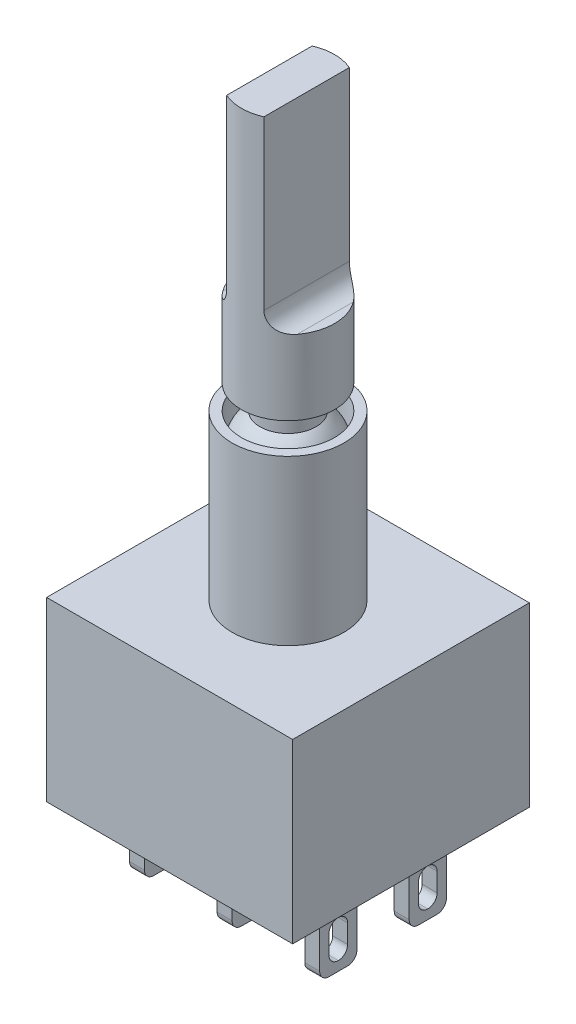
SolidWorks part; units mm, degrees
ref_plane "Спереди" through (0, 0, 0) normal (0, 0, 1) x (1, 0, 0)
ref_plane "Сверху" through (0, 0, 0) normal (0, 1, 0) x (1, 0, 0)
ref_plane "Справа" through (0, 0, 0) normal (1, 0, 0) x (0, 0, -1)
sketch "Sketch1" plane through (0, 0, 0) normal (0, 1, 0) x (1, 0, 0)
  line L1 (6.6, -6.35) -> (-6.6, -6.35)
  line L2 (6.6, -6.35) -> (6.6, 6.35)
  line L3 (6.6, 6.35) -> (-6.6, 6.35)
  line L4 (-6.6, -6.35) -> (-6.6, 6.35)
  line L5 (6.6, -6.35) -> (-6.6, 6.35) construction
  line L6 (6.6, 6.35) -> (-6.6, -6.35) construction
  point P0 (0, 0)
  dimension "D1" = 13.2
  dimension "D2" = 12.7
extrude "Boss-Extrude1" add sketch "Sketch1" along normal blind 9.5
sketch "Sketch2" plane through (0, 9.5, 0) normal (0, 1, 0) x (1, 0, 0)
  line L0 (-6.6, 6.35) -> (6.6, -6.35) construction
  circle A0 centre (0, 0) radius 3
  dimension "D1" = 6
extrude "Boss-Extrude2" add sketch "Sketch2" along normal blind 8.8
sketch "Sketch4" plane through (0, 18.3, 0) normal (0, 1, 0) x (1, 0, 0)
  circle A0 centre (0, 0) radius 2.5
  dimension "D1" = 5
extrude "Cut-Extrude1" cut sketch "Sketch4" against normal blind 2
sketch "Sketch5" plane through (0, 16.3, 0) normal (0, 1, 0) x (1, 0, 0)
  circle A0 centre (0, 0) radius 1.5
  dimension "D1" = 3
extrude "Boss-Extrude3" add sketch "Sketch5" along normal blind 5
sketch "Sketch3" plane through (0, 16.3, 0) normal (0, 1, 0) x (1, 0, 0)
  line L0 (0, -3) -> (0, 3) construction
  line L1 (0, -2.5) -> (0, 2.5)
  circle A0 centre (0, 0) radius 3 construction
  arc A1 (0, -2.5) -> (0, 2.5) centre (0, 0) cw
  point P7 (0, 0)
  dimension "D1" = 5
revolve "Revolve2" add sketch "Sketch3" angle 180 about L0
fillet "Fillet1" radius 1 1 edges at (0, 21.3, 1.5)
sketch "Sketch6" plane through (0, 0, 0) normal (0, -1, 0) x (1, 0, 0)
  line L0 (-4.7, 6.35) -> (-4.7, -6.35) construction
  line L1 (-6.6, 6.35) -> (6.6, 6.35) construction
  line L2 (6.6, -6.35) -> (-6.6, -6.35) construction
  line L3 (0, 6.35) -> (0, -6.35) construction
  line L4 (4.7, 6.35) -> (4.7, -6.35) construction
  line L6 (-6.6, 2.4) -> (6.6, 2.4) construction
  line L7 (-4.3, 1.4) -> (-5.1, 1.4)
  line L8 (-4.3, 1.4) -> (-4.3, 3.4)
  line L9 (-4.3, 3.4) -> (-5.1, 3.4)
  line L10 (-5.1, 1.4) -> (-5.1, 3.4)
  line L11 (-4.3, 1.4) -> (-5.1, 3.4) construction
  line L12 (-4.3, 3.4) -> (-5.1, 1.4) construction
  line L13 (-6.6, -6.35) -> (-6.6, 6.35) construction
  line L14 (6.6, 6.35) -> (6.6, -6.35) construction
  line L15 (-6.6, -2.4) -> (6.6, -2.4) construction
  line L16 (-6.6, 0) -> (6.6, 0) construction
  line L17 (-4.3, -3.4) -> (-5.1, -3.4)
  line L18 (-4.3, -3.4) -> (-4.3, -1.4)
  line L19 (-4.3, -1.4) -> (-5.1, -1.4)
  line L20 (-5.1, -3.4) -> (-5.1, -1.4)
  line L21 (-4.3, -3.4) -> (-5.1, -1.4) construction
  line L22 (-4.3, -1.4) -> (-5.1, -3.4) construction
  line L23 (0.4, -3.4) -> (-0.4, -3.4)
  line L24 (0.4, -3.4) -> (0.4, -1.4)
  line L25 (0.4, -1.4) -> (-0.4, -1.4)
  line L26 (-0.4, -3.4) -> (-0.4, -1.4)
  line L27 (0.4, -3.4) -> (-0.4, -1.4) construction
  line L28 (0.4, -1.4) -> (-0.4, -3.4) construction
  line L29 (0.4, 1.4) -> (-0.4, 1.4)
  line L30 (0.4, 1.4) -> (0.4, 3.4)
  line L31 (0.4, 3.4) -> (-0.4, 3.4)
  line L32 (-0.4, 1.4) -> (-0.4, 3.4)
  line L33 (0.4, 1.4) -> (-0.4, 3.4) construction
  line L34 (0.4, 3.4) -> (-0.4, 1.4) construction
  line L35 (5.1, 1.4) -> (4.3, 1.4)
  line L36 (5.1, 1.4) -> (5.1, 3.4)
  line L37 (5.1, 3.4) -> (4.3, 3.4)
  line L38 (4.3, 1.4) -> (4.3, 3.4)
  line L39 (5.1, 1.4) -> (4.3, 3.4) construction
  line L40 (5.1, 3.4) -> (4.3, 1.4) construction
  line L41 (5.1, -3.4) -> (4.3, -3.4)
  line L42 (5.1, -3.4) -> (5.1, -1.4)
  line L43 (5.1, -1.4) -> (4.3, -1.4)
  line L44 (4.3, -3.4) -> (4.3, -1.4)
  line L45 (5.1, -3.4) -> (4.3, -1.4) construction
  line L46 (5.1, -1.4) -> (4.3, -3.4) construction
  point P10 (0, 0)
  point P11 (-4.7, 2.4)
  point P27 (-4.7, -2.4)
  point P32 (0, -2.4)
  point P37 (0, 2.4)
  point P42 (4.7, 2.4)
  point P47 (4.7, -2.4)
  dimension "D1" = 4.7
  dimension "D2" = 4.7
  dimension "D3" = 2
  dimension "D4" = 0.8
  dimension "D5" = 4.8
  dimension "D6" = 2.4
extrude "Boss-Extrude4" add sketch "Sketch6" along normal blind 4
sketch "Sketch7" plane through (-5.1, 0, 0) normal (-1, 0, 0) x (0, 0, 1)
  line L0 (-2.4, -4) -> (-2.4, 0) construction
  line L1 (-1.4, -4) -> (-3.4, -4) construction
  line L2 (-1.4, 0) -> (-3.4, 0) construction
  line L3 (2.4, -4) -> (2.4, 0) construction
  line L6 (3.4, -4) -> (1.4, -4) construction
  line L7 (3.4, 0) -> (1.4, 0) construction
  line L8 (-3.4, -2.5) -> (3.4, -2.5) construction
  line L9 (-1.9, -3.5) -> (-2.9, -3.5)
  line L10 (-1.9, -3.5) -> (-1.9, -1.5)
  line L11 (-1.9, -1.5) -> (-2.9, -1.5)
  line L12 (-2.9, -3.5) -> (-2.9, -1.5)
  line L13 (-1.9, -3.5) -> (-2.9, -1.5) construction
  line L14 (-1.9, -1.5) -> (-2.9, -3.5) construction
  line L15 (2.9, -3.5) -> (1.9, -3.5)
  line L16 (2.9, -3.5) -> (2.9, -1.5)
  line L17 (2.9, -1.5) -> (1.9, -1.5)
  line L18 (1.9, -3.5) -> (1.9, -1.5)
  line L19 (2.9, -3.5) -> (1.9, -1.5) construction
  line L20 (2.9, -1.5) -> (1.9, -3.5) construction
  line L21 (-3.4, -4) -> (-3.4, 0) construction
  line L22 (3.4, -4) -> (3.4, 0) construction
  point P12 (-2.4, -2.5)
  point P17 (2.4, -2.5)
  dimension "D1" = 0.5
  dimension "D2" = 2
  dimension "D3" = 1
extrude "Cut-Extrude2" cut sketch "Sketch7" against normal through all
fillet "Fillet2" radius 0.5 36 edges at (4.7, -3.5, 2.9) (4.7, -3.5, 1.9) (4.7, -3.5, -1.9) (4.7, -3.5, -2.9) (4.7, -1.5, -1.9) (4.7, -1.5, 2.9) (4.7, -1.5, 1.9) (4.7, -1.5, -2.9) (0, -1.5, 1.9) (0, -1.5, 2.9) (0, -3.5, 2.9) (0, -3.5, 1.9) (0, -3.5, -1.9) (0, -3.5, -2.9) (0, -1.5, -2.9) (0, -1.5, -1.9) (-4.7, -3.5, 2.9) (-4.7, -1.5, 2.9) (-4.7, -3.5, 1.9) (-4.7, -1.5, 1.9) (-4.7, -1.5, -1.9) (-4.7, -1.5, -2.9) (-4.7, -3.5, -1.9) (-4.7, -3.5, -2.9) (0, -4, -1.4) (0, -4, -3.4) (4.7, -4, -1.4) (4.7, -4, -3.4) (4.7, -4, 1.4) (4.7, -4, 3.4) (0, -4, 3.4) (0, -4, 1.4) (-4.7, -4, 3.4) (-4.7, -4, 1.4) (-4.7, -4, -1.4) (-4.7, -4, -3.4)
sketch "Sketch8" plane through (0, 18.3, 0) normal (0, 1, 0) x (1, 0, 0)
  circle A0 centre (0, 0) radius 2.5
  dimension "D1" = 5
extrude "Boss-Extrude5" add sketch "Sketch8" along normal blind 4 from offset 1.3
sketch "Sketch9" plane through (0, 23.6, 0) normal (0, 1, 0) x (1, 0, 0)
  line L0 (0, -2.5) -> (0, 2.5) construction
  line L1 (-1, -2.2913) -> (-1, 2.2913)
  line L2 (1, 2.2913) -> (1, -2.2913)
  circle A0 centre (0, 0) radius 2.5 construction
  arc A1 (-1, -2.2913) -> (1, -2.2913) centre (0, 0) ccw
  arc A2 (-1, 2.2913) -> (1, 2.2913) centre (0, 0) cw
  dimension "D1" = 2
  dimension "D2" = 1
extrude "Boss-Extrude6" add sketch "Sketch9" along normal blind 10
fillet "Fillet3" radius 1 2 edges at (-1, 23.6, 0) (1, 23.6, 0)
